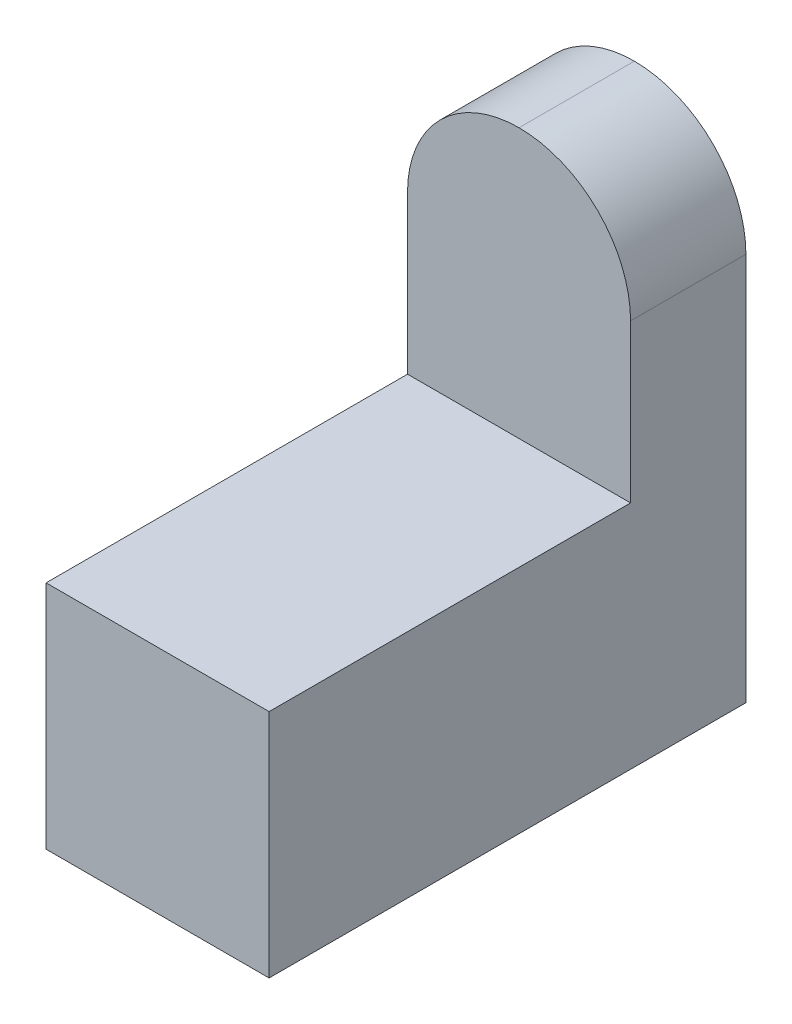
SolidWorks part; units mm, degrees
material "ABS"
ref_plane "Front Plane" through (0, 0, 0) normal (1, 0, 0) x (0, 1, 0)
ref_plane "Top Plane" through (0, 0, 0) normal (0, 0, 1) x (0, 1, 0)
ref_plane "Right Plane" through (0, 0, 0) normal (0, 1, 0) x (-1, 0, 0)
sketch "Sketch1" plane through (0, 0, 0) normal (1, 0, 0) x (0, 1, 0)
  line L0 (0, 0) -> (0, 62)
  line L1 (0, 62) -> (30, 62)
  line L2 (30, 62) -> (30, 15)
  line L3 (30, 15) -> (65, 15)
  line L4 (65, 15) -> (65, 0)
  line L5 (65, 0) -> (0, 0)
  dimension "D1" = 62
  dimension "D2" = 30
  dimension "D3" = 47
  dimension "D4" = 35
  dimension "D5" = 15
extrude "Boss-Extrude1" add sketch "Sketch1" along normal mid plane 29
fillet "Fillet2" radius 14.5 2 edges at (-14.5, 65, 7.5) (14.5, 65, 7.5)
